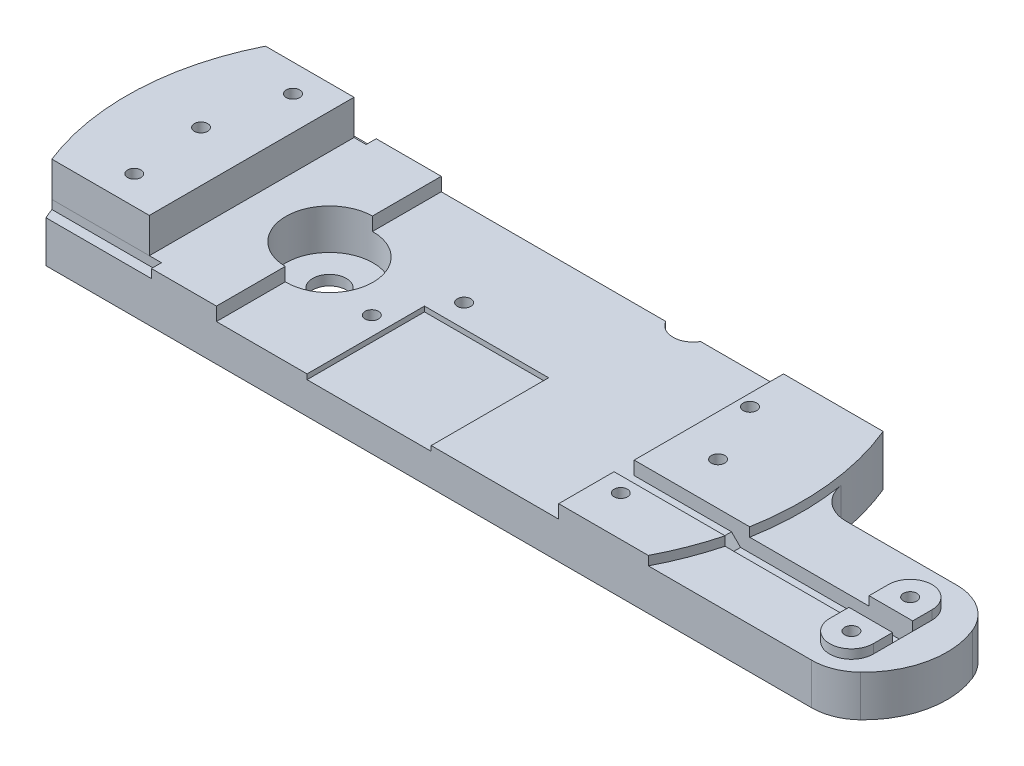
SolidWorks part; units mm, degrees
ref_plane "Front Plane" through (0, 0, 0) normal (0, 0, 1) x (1, 0, 0)
ref_plane "Top Plane" through (0, 0, 0) normal (0, 1, 0) x (1, 0, 0)
ref_plane "Right Plane" through (0, 0, 0) normal (1, 0, 0) x (0, 0, -1)
sketch "Sketch1" plane through (0, 0, 0) normal (0, 1, 0) x (1, 0, 0)
  line L1 (-97.5, -33.5) -> (97.5, -33.5)
  line L2 (-97.5, -33.5) -> (-97.5, 33.5)
  line L3 (-97.5, 33.5) -> (97.5, 33.5)
  line L4 (97.5, -33.5) -> (97.5, 33.5)
  line L5 (-97.5, -33.5) -> (97.5, 33.5) construction
  line L6 (-97.5, 33.5) -> (97.5, -33.5) construction
  point P0 (0, 0)
  dimension "D1" = 67
  dimension "D2" = 195
extrude "Boss-Extrude1" add sketch "Sketch1" along normal blind 25.4
sketch "Sketch2" plane through (0, 0, 0) normal (0, -1, 0) x (1, 0, 0)
  line L0 (-97.5, -33.5) -> (-97.5, 33.5) construction
  line L1 (97.5, 33.5) -> (97.5, -33.5) construction
  line L2 (97.5, 33.5) -> (88.5, 33.5)
  line L3 (-97.5, 33.5) -> (97.5, 33.5) construction
  line L4 (97.5, -33.5) -> (91.5, -33.5)
  line L5 (97.5, -33.5) -> (-97.5, -33.5) construction
  line L6 (-97.5, 33.5) -> (-91, 33.5)
  line L7 (-97.5, -33.5) -> (-88, -33.5)
  circle A0 centre (18.0922, -3.2198) radius 79.4078
  circle A1 centre (-22.6589, 2.9929) radius 74.8411
  line M7 (97.5, -33.5) -> (97.5, 33.5)
  line M8 (97.5, 33.5) -> (-97.5, 33.5)
  line M9 (-97.5, 33.5) -> (-97.5, -33.5)
  line M10 (-97.5, -33.5) -> (97.5, -33.5)
  dimension "D1" = 9
  dimension "D2" = 6
  dimension "D3" = 6.5
  dimension "D4" = 9.5
extrude "Cut-Extrude1" cut sketch "Sketch2" against normal through all contours A0 M7 M8 | A0 M10 M7 | A1 M9 M10 | A1 M8 M9 region at (94.8284, 0, 24.4273) region at (95.7123, 0, -25.9883) region at (-95.5654, 0, 25.941) region at (-94.6839, 0, -24.4966)
sketch "Sketch3" plane through (0, 0, 33.5) normal (0, 0, -1) x (-1, 0, 0)
  line L0 (97.5, 25.4) -> (63.2, 25.4)
  line L2 (63.2, 25.4) -> (63.2, 15)
  line L3 (63.2, 15) -> (40.2, 15)
  line L4 (40.2, 15) -> (40.2, 11)
  line L5 (40.2, 11) -> (-61.8, 11)
  line L6 (-91.5, 25.4) -> (88, 25.4) construction
  line L10 (97.5, 0) -> (97.5, 25.4) construction
  line L11 (-61.8, 11) -> (-61.8, 15)
  line L12 (-61.8, 15) -> (-97.5, 15)
  line L13 (-97.5, 25.4) -> (-97.5, 0) construction
  line L14 (-97.5, 15) -> (-97.5, 25.4)
  line L15 (-97.5, 25.4) -> (63.2, 25.4)
  line M13 (-88.5, 0) -> (-88.5, 25.4)
  line M14 (-88.5, 25.4) -> (91, 25.4)
  dimension "D1" = 10.4
  dimension "D2" = 34.3
  dimension "D3" = 23
  dimension "D4" = 4
  dimension "D5" = 102
extrude "Cut-Extrude2" cut sketch "Sketch3" along normal through all contours L11 L12 L2 L3 L4 L5 M13 M14 | L2 L3 L4 L5 L11 L12 L14 L15 region at (12.2699, 18.7206, 33.5)
sketch "Sketch4" plane through (0, 25.4, 0) normal (0, 1, 0) x (1, 0, 0)
  line L0 (-59.5873, 33.5) -> (-59.5873, 30.5)
  line L1 (-63.2, 33.5) -> (-88, 33.5) construction
  line L2 (-59.5873, 30.5) -> (-89.5873, 30.5)
  line L3 (-59.5873, -33.5) -> (-59.5873, -30.5)
  line L4 (-91, -33.5) -> (-63.2, -33.5) construction
  line L5 (-59.5873, -30.5) -> (-92.2617, -30.5)
  line L6 (-59.5873, 33.5) -> (-63.2, 33.5)
  line L7 (-59.5873, -33.5) -> (-63.2, -33.5)
  arc A0 (-88, 33.5) -> (-91, -33.5) centre (-22.6589, -2.9929) ccw construction
  line M5 (-91, -33.5) -> (-63.2, -33.5)
  line M6 (-63.2, -33.5) -> (-63.2, 33.5)
  line M7 (-63.2, 33.5) -> (-88, 33.5)
  arc M8 (-88, 33.5) -> (-91, -33.5) centre (-22.6589, -2.9929) ccw
  dimension "D1" = 3
  dimension "D2" = 3
  dimension "D3" = 30
extrude "Cut-Extrude3" cut sketch "Sketch4" against normal blind 13 contours L2 M6 M7 M8 | L0 L6 L2 M6 | L5 M6 M8 M5 | L7 L3 L5 M6 region at (-61.3937, 25.4, -32) region at (-76.0082, 25.4, -31.9845) region at (-77.4242, 25.4, 31.9889) region at (-61.3937, 25.4, 32)
sketch "Sketch6" plane through (0, 0, 0) normal (0, -1, 0) x (1, 0, 0)
  line L0 (-63.2, -33.5) -> (-97.5, -33.5)
  line L1 (91.5, -33.5) -> (-88, -33.5) construction
  line L2 (-63.2, -33.5) -> (-63.2, 33.5)
  line L3 (-91, 33.5) -> (88.5, 33.5) construction
  line L4 (-63.2, -9) -> (-28.1, -9) construction
  line L5 (-63.2, 8.7) -> (-18.7, 8.7) construction
  line L6 (-63.2, -8.3) -> (-8.2, -8.3) construction
  line L8 (91.5, -33.5) -> (-88, -33.5) construction
  line L9 (-97.5, -33.5) -> (-97.5, 33.5)
  line L10 (-97.5, 33.5) -> (-63.2, 33.5)
  circle A1 centre (-18.7, 8.7) radius 2
  circle A2 centre (74.1, -1.7) radius 2
  circle A3 centre (68.3, 21.5) radius 2
  circle A4 centre (65.3, -20) radius 2
  circle A5 centre (-8.2, -8.3) radius 2
  circle A6 centre (-76.2, 22) radius 2
  circle A7 centre (-78.2, 0.1) radius 2
  circle A8 centre (-73.2, -22.3) radius 2
  arc A10 (-91, 33.5) -> (-88, -33.5) centre (-22.6589, 2.9929) ccw construction
  dimension "D22" = 4
  dimension "D3" = 35.1
  dimension "D4" = 34.3
  dimension "D5" = 44.5
  dimension "D6" = 24.5
  dimension "D7" = 55
  dimension "D8" = 42.2
  dimension "D9" = 137.3
  dimension "D10" = 128.5
  dimension "D11" = 131.5
  dimension "D12" = 10
  dimension "D13" = 15
  dimension "D14" = 13
  dimension "D15" = 11.2
  dimension "D16" = 33.6
  dimension "D17" = 55.5
  dimension "D18" = 31.8
  dimension "D19" = 55
  dimension "D20" = 13.5
  dimension "D21" = 25.2
extrude "Cut-Extrude4" cut sketch "Sketch6" against normal through all contours A5 | A1 | A6 | A7 | A8 | A4 | A2 | A3 region at (-18.7, 0, 8.7) region at (74.1, 0, -1.7) region at (68.3, 0, 21.5) region at (65.3, 0, -20) region at (-8.2, 0, -8.3) region at (-76.2, 0, 22) region at (-78.2, 0, 0.1) region at (-73.2, 0, -22.3)
sketch "Sketch7" plane through (0, 11, 0) normal (0, 1, 0) x (1, 0, 0)
  line L1 (-13.2, 1.5) -> (23.8, 1.5)
  line L2 (-13.2, 1.5) -> (-13.2, -33.5)
  line L3 (-13.2, -33.5) -> (23.8, -33.5)
  line L4 (23.8, 1.5) -> (23.8, -33.5)
  line L8 (-63.2, 30.5) -> (-63.2, -30.5) construction
  line L9 (-63.2, 30.5) -> (-63.2, -30.5) construction
  line L10 (-40.2, -33.5) -> (61.8, -33.5) construction
  dimension "D1" = 50
  dimension "D2" = 87
  dimension "D3" = 35
extrude "Cut-Extrude5" cut sketch "Sketch7" against normal blind 1.5
sketch "Sketch8" plane through (0, 25.4, 0) normal (0, 1, 0) x (1, 0, 0)
  line L0 (-59.5873, -33.5) -> (-97.5, -33.5)
  line L1 (-97.5, -33.5) -> (-97.5, 33.5)
  line L3 (-97.5, 33.5) -> (31.9, 33.5)
  line L6 (31.9, 36.5) -> (31.9, 30.5)
  line L7 (31.9, 33.5) -> (37.0962, 33.5)
  line L10 (-59.5873, 33.5) -> (-88, 33.5) construction
  line L11 (-40.2, 33.5) -> (61.8, 33.5) construction
  circle A1 centre (31.9, 36.5) radius 6
  arc A2 (-89.5873, 30.5) -> (-92.2617, -30.5) centre (-22.6589, -2.9929) ccw construction
  dimension "D1" = 12
  dimension "D2" = 129.4
extrude "Cut-Extrude6" cut sketch "Sketch8" against normal blind 18.5 contours L6 A1 L7 | L3 A1 L6 region at (29.8648, 25.4, -32.2699) region at (33.9352, 25.4, -32.2699)
sketch "Sketch9" plane through (0, 0, 0) normal (0, -1, 0) x (1, 0, 0)
  line L0 (88.5, 33.5) -> (137.2004, 33.5)
  line L1 (139.5727, -7.5) -> (97.3846, -7.5)
  arc A0 (153.4738, 1.8643) -> (147.5429, 29.3643) centre (130.3054, 11.2571) ccw
  arc A1 (91.5, -33.5) -> (88.5, 33.5) centre (18.0922, -3.2198) ccw construction
  arc A2 (142.3827, -10.6321) -> (147.5429, 29.3643) centre (130.3054, 11.2571) ccw construction
  arc A3 (147.5429, 29.3643) -> (137.2004, 33.5) centre (137.2004, 18.5) ccw
  arc A4 (147.5429, 29.3643) -> (137.9704, 33.4802) centre (137.2004, 18.5) ccw construction
  arc A5 (139.5727, -7.5) -> (153.4738, 1.8643) centre (139.5727, 7.5) ccw
  circle A6 centre (112.8948, -27.5) radius 16 construction
  circle A7 centre (103.4238, 59.4942) radius 16 construction
  circle A8 centre (112.8948, -27.5) radius 20 construction
  arc A9 (97.3846, -7.5) -> (88.5, 33.5) centre (18.0922, -3.2198) ccw
  circle A10 centre (138.3, 5.25) radius 2
  circle A11 centre (138.3, 22.75) radius 2
  circle A12 centre (138.3, 22.75) radius 2 construction
  circle A13 centre (138.3, 5.25) radius 2 construction
  dimension "D1" = 4
extrude "Boss-Extrude2" add sketch "Sketch9" against normal offset from surface (12.3 mm away) 1.3 up to face at (-16.7, 11, 8.7) offset beyond the face yes
fillet "Fillet1" radius 10 1 edges at (97.3846, 6.15, -7.5)
sketch "Sketch10" plane through (0, 0, 0) normal (0, -1, 0) x (1, 0, 0)
  circle A0 centre (-40.0178, 0) radius 13
  dimension "D1" = 26
extrude "Cut-Extrude7" cut sketch "Sketch10" against normal up to surface (15 mm away) from offset 3 up to face at (-55.6437, 15, 0) offset against normal yes
sketch "Sketch13" plane through (0, 0, 0) normal (0, -1, 0) x (1, 0, 0)
  circle A0 centre (-40.0178, 0) radius 5
  dimension "D1" = 10
extrude "Cut-Extrude9" cut sketch "Sketch13" against normal through all
sketch "Sketch11" plane through (0, 12.3, 0) normal (0, 1, 0) x (1, 0, 0)
  line L0 (138.3, -5.25) -> (138.3, -22.75) construction
  line L1 (144.8, -5.25) -> (144.8, -22.75)
  line L2 (131.8, -5.25) -> (131.8, -22.75)
  line L3 (131.8, -11) -> (144.8, -11)
  line L4 (131.8, -17) -> (144.8, -17)
  line L5 (131.8, -14) -> (144.8, -14) construction
  arc A0 (144.8, -5.25) -> (131.8, -5.25) centre (138.3, -5.25) ccw
  arc A1 (131.8, -22.75) -> (144.8, -22.75) centre (138.3, -22.75) ccw
  point P4 (138.3, -14)
  circle M15 centre (138.3, -22.75) radius 2
  circle M16 centre (138.3, -5.25) radius 2
  dimension "D1" = 13
  dimension "D2" = 6
extrude "Boss-Extrude3" add sketch "Sketch11" along normal up to surface (2.7 mm away) contours L1 A0 L2 L3 M16 | L2 A1 L1 L4 M15 region at (144.6214, 12.3, 8.125) region at (144.6214, 12.3, 19.875) up to face at (70.3, 15, 21.5)
split "Split1" bodies to split 113 resulting bodies 114 115 split by face at (-53.8367, 15, 0)
sketch "Sketch12" plane through (0, 0, 11) normal (0, 0, 1) x (1, 0, 0)
  line L0 (144.8, 15) -> (144.8, 8.3)
  line L1 (144.8, 8.3) -> (93.5, 8.3)
  line L3 (97.5, 12.3) -> (88.5, 12.3) construction
  line L4 (90.8, 11) -> (61.8, 11)
  line L5 (61.8, 11) -> (61.8, 15)
  line L6 (61.8, 15) -> (88.5, 15) construction
  line L7 (61.8, 15) -> (144.8, 15)
  line L10 (97.5, 12.3) -> (93.5, 12.3) construction
  line L12 (88.5, 12.3) -> (137.2004, 12.3) construction
  line L13 (93.5, 12.3) -> (93.5, 8.3) construction
  line L14 (61.8, 11) -> (61.8, 15) construction
  line L15 (23.8, 11) -> (61.8, 11) construction
  line L16 (93.5, 8.3) -> (90.8, 11)
  dimension "D1" = 45
extrude "Cut-Extrude8" cut sketch "Sketch12" along normal up to surface (6 mm away) up to face at (138.3, 13.65, 17)
